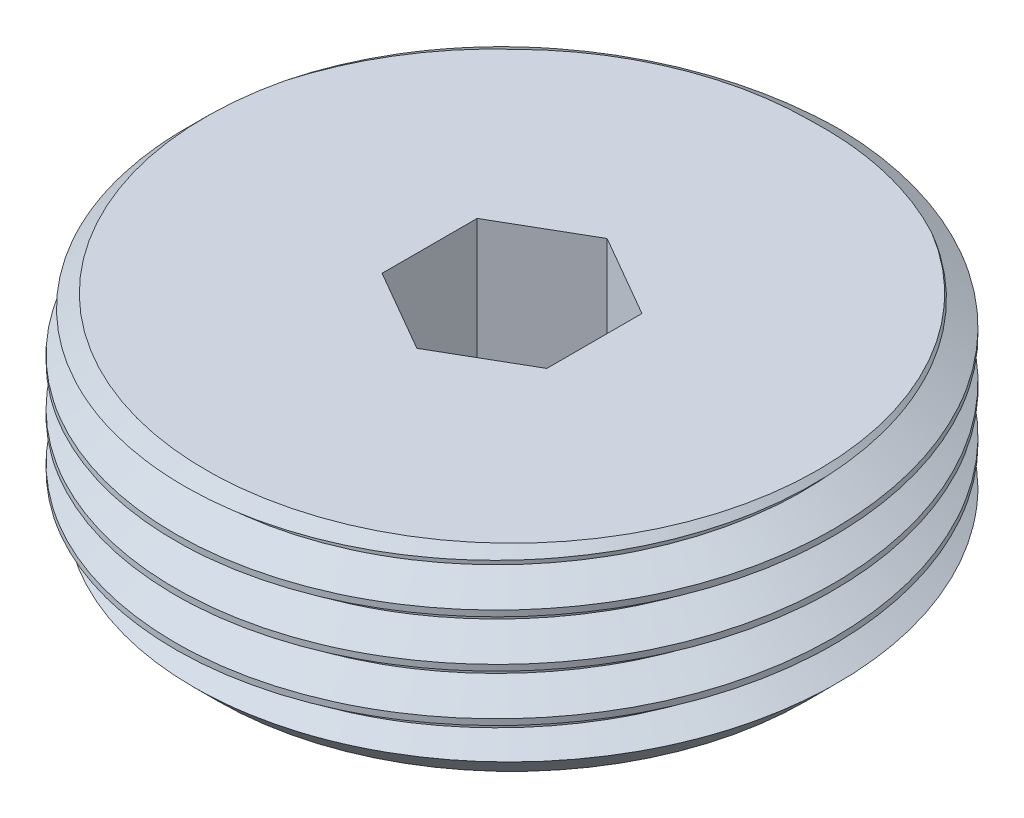
SolidWorks part; units mm, degrees
ref_plane "Front Plane" through (0, 0, 0) normal (0, 0, 1) x (1, 0, 0)
ref_plane "Top Plane" through (0, 0, 0) normal (0, 1, 0) x (1, 0, 0)
ref_plane "Right Plane" through (0, 0, 0) normal (1, 0, 0) x (0, 0, -1)
sketch "Sketch1" plane through (0, 0, 0) normal (0, 1, 0) x (1, 0, 0)
  circle A0 centre (0, 0) radius 12.7
  dimension "OD" = 25.4
extrude "Extrude1" add sketch "Sketch1" against normal blind 7.9375
sketch "Sketch2" plane through (0, 0, 0) normal (0, 1, 0) x (1, 0, 0)
  circle A0 centre (0, 0) radius 12.7 construction
  circle A1 centre (0, 0) radius 12.7
  point P3 (0, -12.7)
curve "Helix/Spiral1" pitch 1.8143 height 9.7518 turns 5.375 parameters "pitch"=1.8143
chamfer "Chamfer1" distance 1.3607 angle 45 1 edges at (0, -7.9375, 12.7)
chamfer "Chamfer2" distance 0.9071 angle 45 1 edges at (0, 0, 12.7)
sketch "Sketch3" plane through (0, 0, 0) normal (1, 0, 0) x (0, 0, -1)
  line L0 (-12.7, 0) -> (-11.5216, 0.6804)
  line L1 (-11.5216, 0.6804) -> (-11.5216, 0.9071)
  line L2 (-11.5216, 0.9071) -> (-12.7, 1.5875)
  line L3 (-12.7, 1.5875) -> (-12.7, 0)
  line L4 (-11.5216, 0.7937) -> (-12.7, 0.7937) construction
  line L5 (-12.1108, 0.3402) -> (-12.1108, 1.2473) construction
  line L6 (-12.7, 1.5875) -> (-12.9268, 1.7184) construction
  line L7 (-12.9268, 1.7184) -> (-12.9268, -0.1309) construction
  line L8 (-12.9268, -0.1309) -> (-12.7, 0) construction
  line L9 (-12.7, 0.7937) -> (-12.9268, 0.7937) construction
  line L10 (-11.5216, 0.7937) -> (12.7, 0.7937) construction
  line L11 (12.7, 0.7937) -> (12.7, -1.0556) construction
  line L12 (12.7, -1.0556) -> (12.7, -2.905) construction
  line L13 (12.7, -2.905) -> (12.7, -4.7544) construction
  line L14 (12.7, -6.5768) -> (12.7, -0.9071) construction
  dimension "D1" = 0.2268
  dimension "D2" = 0.9071
  dimension "D3" = 60
sweep "Cut-Sweep1" cut profiles "Sketch3" path "Helix/Spiral1"
sketch "Sketch4" plane through (0, 0, 0) normal (0, 1, 0) x (1, 0, 0)
  line L1 (0, 3.6662) -> (-3.175, 1.8331)
  line L2 (-3.175, 1.8331) -> (-3.175, -1.8331)
  line L3 (-3.175, -1.8331) -> (0, -3.6662)
  line L4 (0, -3.6662) -> (3.175, -1.8331)
  line L5 (3.175, -1.8331) -> (3.175, 1.8331)
  line L6 (3.175, 1.8331) -> (0, 3.6662)
  circle A0 centre (0, 0) radius 3.175 construction
  dimension "hex" = 6.35
extrude "Cut-Extrude1" cut sketch "Sketch4" against normal through all
equation "\"D1@Chamfer1\" = \"pitch@Helix/Spiral1\" * 3 / 4"
equation "\"D1@Chamfer2\" = \"pitch@Helix/Spiral1\" * 1 / 2"
equation "\"D3@Helix/Spiral1\" = \"height@Extrude1\" + \"pitch@Helix/Spiral1\""
equation "\"D1@Sketch3\" = \"pitch@Helix/Spiral1\"*.125"
equation "\"D2@Sketch3\" = \"pitch@Helix/Spiral1\"*.50"
